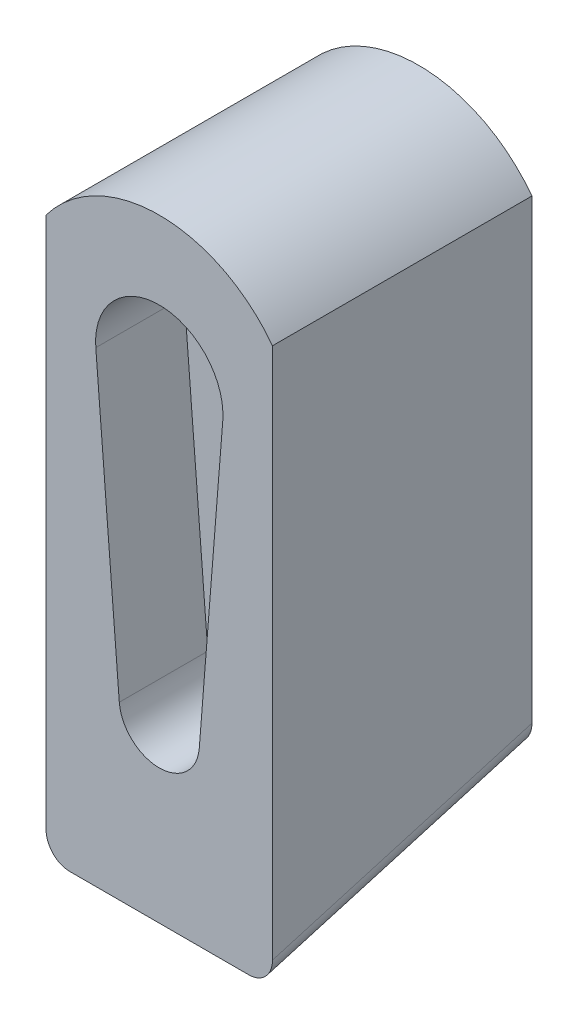
SolidWorks part; units mm, degrees
material "ABS"
ref_plane "Front Plane" through (0, 0, 0) normal (0, 0, 1) x (1, 0, 0)
ref_plane "Top Plane" through (0, 0, 0) normal (0, 1, 0) x (1, 0, 0)
ref_plane "Right Plane" through (0, 0, 0) normal (1, 0, 0) x (0, 0, -1)
sketch "Sketch1" plane through (0, 0, 0) normal (0, 0, 1) x (1, 0, 0)
  line L0 (-6.096, 4.572) -> (-6.096, -33.528)
  line L1 (-6.096, -33.528) -> (6.096, -33.528)
  line L2 (6.096, -33.528) -> (6.096, 4.572)
  arc A0 (-6.096, 4.572) -> (6.096, 4.572) centre (0, 0) cw
  point P7 (0, -33.528)
  dimension "D1" = 7.62
  dimension "D3" = 38.1
  dimension "D2" = 12.192
extrude "Boss-Extrude1" add sketch "Sketch1" along normal blind 13.97
sketch "Sketch2" plane through (0, 0, 13.97) normal (0, 0, 1) x (1, 0, 0)
  line L0 (3.4182, -0.2721) -> (2.1522, -16.1733)
  line L1 (-2.1522, -16.1733) -> (-3.4182, -0.2721)
  arc A0 (3.4182, -0.2721) -> (-3.4182, -0.2721) centre (0, 0) ccw
  arc A1 (2.1522, -16.1733) -> (-2.1522, -16.1733) centre (0, -16.002) cw
  dimension "D1" = 3.429
  dimension "D2" = 2.159
  dimension "D3" = 16.002
extrude "Cut-Extrude1" cut sketch "Sketch2" against normal blind 4.7625 and the other way through all
sketch "Sketch3" plane through (6.096, 0, 0) normal (1, 0, 0) x (0, 0, -1)
  line L0 (-13.97, -33.528) -> (-13.97, 4.572) construction
  line L1 (-13.97, -33.528) -> (-13.97, -25.4)
  line L2 (-13.97, -25.4) -> (0, -21.336)
  line L3 (0, -33.528) -> (0, 4.572) construction
  line L4 (0, -21.336) -> (0, -33.528)
  line L5 (0, -33.528) -> (-13.97, -33.528)
  dimension "D1" = 8.128
  dimension "D2" = 12.192
extrude "Cut-Extrude2" cut sketch "Sketch3" against normal through all
sketch "Sketch4" plane through (0, 0, 9.2075) normal (0, 0, 1) x (1, 0, 0)
  circle A0 centre (0, 0) radius 1.5875
  dimension "D1" = 3.175
extrude "Cut-Extrude3" cut sketch "Sketch4" against normal through all
sketch "Sketch5" plane through (0, 0, 0) normal (0, 0, -1) x (-1, 0, 0)
  circle A0 centre (0, 0) radius 3.175
  dimension "D1" = 6.35
extrude "Cut-Extrude4" cut sketch "Sketch5" against normal blind 6.35
chamfer "Chamfer1" distance 1.016 angle 45 1 edges at (-3.175, 0, 6.35)
fillet "Fillet1" radius 1.27 2 edges at (-6.096, -23.368, 6.985) (6.096, -23.368, 6.985)
